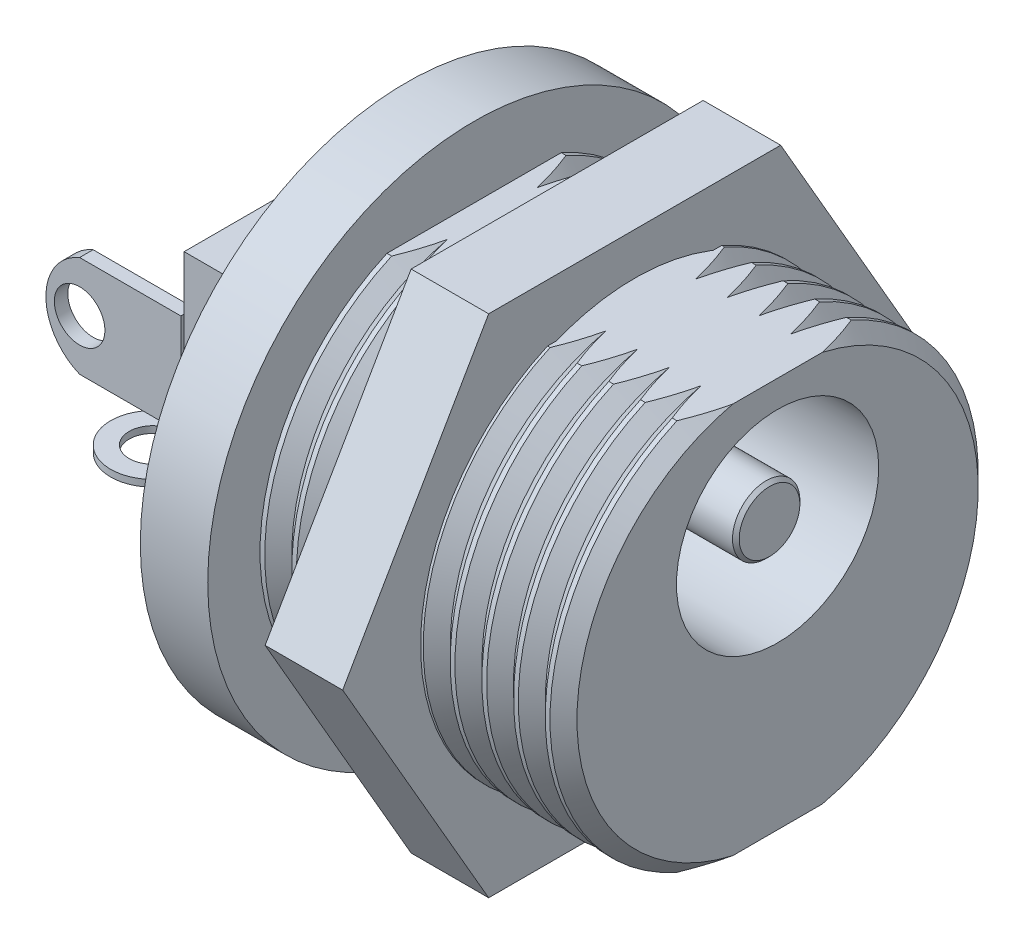
SolidWorks part; units mm, degrees
ref_plane "Front" through (0, 0, 0) normal (0, 0, 1) x (1, 0, 0)
ref_plane "Top" through (0, 0, 0) normal (0, 1, 0) x (1, 0, 0)
ref_plane "Right" through (0, 0, 0) normal (1, 0, 0) x (0, 0, -1)
ref_plane "Plane2" [suppressed] through (0, 0, 0.35) normal (0, 0, 1) x (1, 0, 0)
sketch "Sketch82" plane through (0, 0, 0) normal (1, 0, 0) x (0, 0, -1)
  circle A0 centre (0, 0) radius 6.35
  dimension "D1" = 12.7
extrude "Extrude34" add sketch "Sketch82" against normal blind 9
sketch "Sketch83" plane through (-9, 0, 0) normal (-1, 0, 0) x (0, 0, 1)
  circle A0 centre (0, 0) radius 7.9
  dimension "D1" = 15.8
extrude "Extrude35" add sketch "Sketch83" along normal blind 2
sketch "Sketch84" plane through (-11, 0, 0) normal (-1, 0, 0) x (0, 0, 1)
  line L0 (0, 0) -> (2.5533, 0) construction
  line L1 (-4.6, 4.85) -> (4.6, 4.85)
  line L2 (-4.6, 4.85) -> (-4.6, -4.85)
  line L3 (-4.6, -4.85) -> (4.6, -4.85)
  line L4 (4.6, 4.85) -> (4.6, -4.85)
  line L5 (0, 0) -> (0, -1.3958) construction
  dimension "D1" = 9.2
  dimension "D2" = 9.7
extrude "Extrude36" add sketch "Sketch84" along normal blind 2
sketch "Sketch85" plane through (-13, 0, 0) normal (-1, 0, 0) x (0, 0, 1)
  line L1 (0.63, -3.3) -> (3.13, -3.3)
  line L2 (0.63, -3.3) -> (0.63, -3.5)
  line L3 (0.63, -3.5) -> (3.13, -3.5)
  line L4 (3.13, -3.3) -> (3.13, -3.5)
  line L5 (-2.77, -1.1) -> (-0.27, -1.1)
  line L6 (-2.77, -1.1) -> (-2.77, -1.4)
  line L7 (-2.77, -1.4) -> (-0.27, -1.4)
  line L8 (-0.27, -1.1) -> (-0.27, -1.4)
  line L9 (4.3, 3.25) -> (4.7, 3.25)
  line L10 (4.3, 3.25) -> (4.3, 0.25)
  line L11 (4.3, 0.25) -> (4.7, 0.25)
  line L12 (4.7, 3.25) -> (4.7, 0.25)
  line L13 (0, 7.9) -> (0, -7.9) construction
  line L14 (-7.9, 0) -> (7.9, 0) construction
  line L15 (1.88, -3.3) -> (1.88, -3.5) construction
  line L16 (-1.52, -1.1) -> (-1.52, -1.4) construction
  line L17 (-2.77, -1.25) -> (-0.27, -1.25) construction
  line L18 (0.63, -3.4) -> (3.13, -3.4) construction
  line L19 (4.5, 3.25) -> (4.5, 0.25) construction
  line L20 (4.3, 1.75) -> (4.7, 1.75) construction
  circle A0 centre (0, 0) radius 7.9 construction
  circle A1 centre (0, 0) radius 7.9 construction
  dimension "D1" = 2.5
  dimension "D2" = 0.2
  dimension "D3" = 4.5
  dimension "D4" = 1.88
  dimension "D5" = 1.52
  dimension "D6" = 1.25
  dimension "D7" = 0.25
  dimension "D8" = 3
  dimension "D9" = 0.3
  dimension "D10" = 0.4
  dimension "D11" = 3.4
extrude "Extrude37" add sketch "Sketch85" along normal blind 4.9
sketch "Sketch86" plane through (0, 0, 4.3) normal (0, 0, -1) x (-1, 0, 0)
  line L0 (17.9, 3.25) -> (13, 3.25) construction
  line L1 (17.9, 0.25) -> (13, 0.25) construction
  line L3 (17, 1.8708) -> (17, 0.9445) construction
  line L4 (13, 4.85) -> (13, -4.85) construction
  line L5 (16, 3.25) -> (17.9, 3.25)
  line L6 (17.9, 3.25) -> (17.9, 0.25)
  line L7 (17.9, 0.25) -> (16, 0.25)
  arc A0 (16, 3.25) -> (16, 0.25) centre (15.375, 1.75) cw
  circle A1 centre (16, 1.75) radius 0.75
  dimension "D1" = 1.625
  dimension "D2" = 4
  dimension "D3" = 1.5
  dimension "D4" = 3
extrude "Cut-Extrude41" cut sketch "Sketch86" against normal blind 4.9
fillet "Fillet25" radius 1.25 4 edges at (-17.9, -3.4, 3.13) (-17.9, -3.4, 0.63) (-17.9, -1.25, -0.27) (-17.9, -1.25, -2.77)
sketch "Sketch87" plane through (0, 0, 0) normal (1, 0, 0) x (0, 0, -1)
  line L0 (-2.5851, 5.8) -> (2.5851, 5.8)
  line L1 (0, 0) -> (2.2361, 0) construction
  line L2 (-2.5851, -5.8) -> (2.5851, -5.8)
  circle A0 centre (0, 2) radius 3
  circle A1 centre (0, 2) radius 1 construction
  circle A2 centre (0, 0) radius 6.35 construction
  arc A3 (2.5851, 5.8) -> (-2.5851, 5.8) centre (0, 0) ccw
  arc A4 (2.5851, -5.8) -> (-2.5851, -5.8) centre (0, 0) cw
  dimension "D1" = 6
  dimension "D3" = 11.6
  dimension "A" = 2
  dimension "D2" = 2
extrude "Cut-Extrude42" cut sketch "Sketch87" against normal up to surface (9 mm away) up to face at (-9, 0, 6.35)
ref_plane "Plane7" through (-4.238, 0, 0) normal (1, 0, 0) x (0, 0, -1)
sketch "Sketch88" plane through (-4.238, 0, 0) normal (1, 0, 0) x (0, 0, -1)
  line L1 (-8.6603, 0) -> (-4.3301, -7.5)
  line L2 (-4.3301, -7.5) -> (4.3301, -7.5)
  line L3 (4.3301, -7.5) -> (8.6603, 0)
  line L4 (8.6603, 0) -> (4.3301, 7.5)
  line L5 (4.3301, 7.5) -> (-4.3301, 7.5)
  line L6 (-4.3301, 7.5) -> (-8.6603, 0)
  circle A0 centre (0, 0) radius 7.5 construction
  circle A1 centre (0, 0) radius 6.25
  arc A2 (2.5851, -5.8) -> (2.5851, 5.8) centre (0, 0) ccw construction
  dimension "D2" = 0.1
  dimension "D1" = 15
extrude "Extrude38" add sketch "Sketch88" against normal blind 2.3 separate body
sketch "Sketch161" plane through (-4.238, 0, 0) normal (1, 0, 0) x (0, 0, -1)
  circle A0 centre (0, 2) radius 1
  circle A1 centre (0, 2) radius 3 construction
  dimension "A" = 2
extrude "Extrude70" add sketch "Sketch161" along normal blind 4
chamfer "Chamfer21" distance 0.1 angle 45 1 edges at (-0.238, 2, -1)
sketch "Sketch193" plane through (-13, 0, 0) normal (-1, 0, 0) x (0, 0, 1)
  line L0 (4.3, 3.25) -> (0, 3.25)
  line L1 (4.3, 0.25) -> (0, 0.25)
  line L2 (4.3, 3.25) -> (4.3, 0.25) construction
  line L3 (4.3, 0.25) -> (4.3, 3.25)
  arc A0 (0, 3.25) -> (0, 0.25) centre (0, 1.75) ccw
  circle A1 centre (0, 2) radius 1 construction
  circle A2 centre (0, 1.75) radius 1
extrude "Extrude82" add sketch "Sketch193" along normal blind 0.3
sketch "Sketch194" plane through (0, -1.4, 0) normal (0, -1, 0) x (1, 0, 0)
  line L0 (-13.5, -0.27) -> (-13.5, -0.67)
  line L1 (-16.65, -0.27) -> (-13, -0.27) construction
  line L2 (-13.5, -0.67) -> (-15.7335, -0.67)
  line L3 (-13.5, -0.27) -> (-16.65, -0.27)
  line L4 (-13, -4.6) -> (-13, 4.6) construction
  line L5 (-16.65, -2.77) -> (-13, -2.77) construction
  line L6 (-13.5, -2.77) -> (-16.65, -2.77)
  line L7 (-13.5, -2.37) -> (-15.7335, -2.37)
  line L8 (-13.5, -2.77) -> (-13.5, -2.37)
  line L9 (-17.9, -1.52) -> (-13, -1.52) construction
  line L10 (-13, -2.77) -> (-13, -0.27) construction
  circle A0 centre (-16.65, -1.52) radius 0.7
  arc A1 (-17.9, -1.52) -> (-16.65, -2.77) centre (-16.65, -1.52) ccw construction
  arc A2 (-15.7335, -0.67) -> (-16.65, -0.27) centre (-16.65, -1.52) ccw
  arc A3 (-15.7335, -2.37) -> (-16.65, -2.77) centre (-16.65, -1.52) cw
  dimension "D1" = 1.4
  dimension "D2" = 0.5
  dimension "D3" = 1.7
sketch "Sketch195" plane through (0, -3.5, 0) normal (0, -1, 0) x (1, 0, 0)
  line L0 (-16.65, 0.63) -> (-13, 0.63) construction
  line L1 (-16.65, 3.13) -> (-13, 3.13) construction
  line L2 (-17.9, 1.88) -> (-13, 1.88) construction
  line L3 (-13, 0.63) -> (-13, 3.13) construction
  line L6 (-13.5, 0.63) -> (-16.65, 0.63)
  line L7 (-13.5, 3.13) -> (-16.65, 3.13)
  line L8 (-13.5, 0.63) -> (-13.5, 1.03)
  line L9 (-13.5, 2.73) -> (-15.7335, 2.73)
  line L10 (-13.5, 1.03) -> (-15.7335, 1.03)
  line L11 (-13.5, 3.13) -> (-13.5, 2.73)
  circle A0 centre (-16.65, 1.88) radius 0.7
  arc A1 (-17.9, 1.88) -> (-16.65, 0.63) centre (-16.65, 1.88) ccw construction
  arc A5 (-15.7335, 1.03) -> (-16.65, 0.63) centre (-16.65, 1.88) cw
  arc A6 (-15.7335, 2.73) -> (-16.65, 3.13) centre (-16.65, 1.88) ccw
  dimension "D1" = 1.4
  dimension "D2" = 1.7
  dimension "D3" = 0.5
extrude "Cut-Extrude103" cut sketch "Sketch194" against normal up to next (0.3 mm away)
extrude "Cut-Extrude104" cut sketch "Sketch195" against normal up to next (0.2 mm away)
sketch "Sketch198" plane through (0, 0, 0) normal (0, 1, 0) x (1, 0, 0)
  line L0 (0, 0) -> (-4.238, 0) construction
  line L1 (-4.238, 4.3301) -> (-4.238, -4.3301) construction
  line L2 (-0.4, 6.35) -> (0, 5.95)
  line L4 (0, 2.5851) -> (0, 6.35) construction
  line L5 (0, 5.95) -> (0.4, 6.35)
  line L6 (0.4, 6.35) -> (-0.4, 6.35)
  line L7 (0, 6.35) -> (-9, 6.35) construction
  dimension "D1" = 0.4
revolve "Cut-Revolve14" cut sketch "Sketch198" angle 360 about L0
pattern_linear "LPattern3" count 10 spacing 0.94 along (-1, 0, 0) of "Cut-Revolve14"
ref_plane "Plane13" [suppressed] through (-2, 0, 0) normal (1, 0, 0) x (0, 0, -1)
ref_plane "Plane24" through (-9, 0, 0) normal (1, 0, 0) x (0, 0, -1)
ref_plane "SIDE_CONNECTOR_PLANE" [suppressed] through (-9, 0, 0) normal (1, 0, 0) x (0, 0, -1)
ref_plane "Plane23" [suppressed] through (-9.1, 0, 0) normal (1, 0, 0) x (0, 0, -1)
